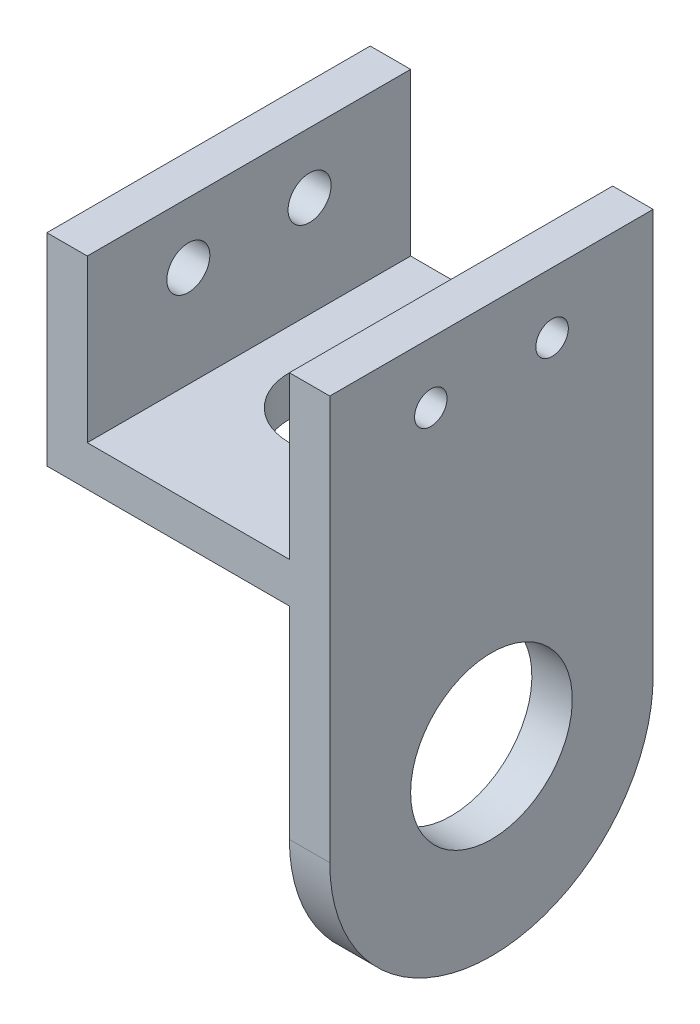
SolidWorks part; units mm, degrees
material "Nylon 101"
ref_plane "Front" through (0, 0, 0) normal (0, 0, 1) x (1, 0, 0)
ref_plane "Top" through (0, 0, 0) normal (0, 1, 0) x (1, 0, 0)
ref_plane "Right" through (0, 0, 0) normal (1, 0, 0) x (0, 0, -1)
sketch "Sketch1" plane through (0, 0, 0) normal (0, 0, 1) x (1, 0, 0)
  line L0 (0, 0) -> (6.35, 0)
  line L1 (6.35, 0) -> (6.35, 88.9)
  line L2 (6.35, 88.9) -> (0, 88.9)
  line L3 (0, 88.9) -> (0, 63.5)
  line L4 (0, 63.5) -> (-31.75, 63.5)
  line L5 (-31.75, 63.5) -> (-31.75, 88.9)
  line L6 (-31.75, 88.9) -> (-38.1, 88.9)
  line L7 (-38.1, 88.9) -> (-38.1, 57.15)
  line L8 (-38.1, 57.15) -> (0, 57.15)
  line L9 (0, 57.15) -> (0, 0)
  point P3 (0, 28.575)
  dimension "D1" = 6.35
  dimension "D2" = 28.575
  dimension "D3" = 31.75
  dimension "D4" = 6.35
  dimension "D5" = 6.35
  dimension "D6" = 25.4
  dimension "D8" = 6.35
extrude "Boss-Extrude1" add sketch "Sketch1" along normal blind 50.8
sketch "Sketch2" plane through (0, 0, 0) normal (-1, 0, 0) x (0, 0, 1)
  line L1 (50.8, 57.15) -> (50.8, 0) construction
  line L2 (50.8, 28.575) -> (0, 28.575) construction
  line L3 (0, 57.15) -> (0, 0) construction
  circle A0 centre (25.4, 28.575) radius 12.7
  dimension "D3" = 25.4
extrude "Cut-Extrude1" cut sketch "Sketch2" against normal blind 44.45
hole_wizard "1/4-20 Tapped Hole1" positions "Sketch3" profile "Sketch4" tap size "1/4-20" standard "ANSI Inch" end condition through all
sketch "Sketch3" plane through (0, 0, 0) normal (-1, 0, 0) x (0, 0, 1)
  line L2 (50.8, 88.9) -> (0, 88.9) construction
  line L3 (0, 88.9) -> (0, 63.5) construction
  point P0 (15.875, 79.375)
  point P2 (34.925, 79.375)
  dimension "D1" = 19.05
  dimension "D2" = 9.525
  dimension "D3" = 15.875
sketch "Sketch4" plane through (0, 79.375, 15.875) normal (0, 1, 0) x (0, 0, 1)
  line L0 (0, 0) -> (0, 6.35)
  line L1 (0, 6.35) -> (2.5527, 6.35)
  line L2 (2.5527, 6.35) -> (2.5527, 0)
  line L5 (2.5527, 0) -> (0, 0)
  line L11 (0, -6.35) -> (0, 107.95) construction
  dimension "Thru Tap Drill Dia." = 5.1054
  dimension "Thru Tap Drill Depth" = 6.35
cosmetic thread "Hole Thread1" parameters "D2"=6.35
cosmetic thread "Hole Thread2" parameters "D2"=6.35
sketch "Sketch5" plane through (-38.1, 0, 0) normal (-1, 0, 0) x (0, 0, 1)
  line L0 (50.8, 88.9) -> (0, 88.9) construction
  line L1 (50.8, 88.9) -> (50.8, 57.15) construction
  circle A0 centre (15.875, 79.375) radius 3.3782
  circle A1 centre (34.925, 79.375) radius 3.3782
  dimension "D4" = 6.7564
  dimension "D1" = 19.05
  dimension "D2" = 9.525
  dimension "D3" = 15.875
extrude "Cut-Extrude2" cut sketch "Sketch5" against normal blind 8.89
sketch "Sketch6" plane through (0, 63.5, 0) normal (0, 1, 0) x (1, 0, 0)
  line L0 (6.35, -50.8) -> (0, -50.8) construction
  line L2 (0, -50.8) -> (0, 0) construction
  circle A0 centre (-15.875, -25.4) radius 9.525
  dimension "D1" = 19.05
  dimension "D2" = 25.4
  dimension "D3" = 15.875
extrude "Cut-Extrude3" cut sketch "Sketch6" against normal blind 8.89
fillet "Fillet1" 2 edges at (3.175, 0, 50.8) (3.175, 0, 0) type full round first side face at (-12.7, 59.69, 50.8) second side face at (-12.7, 59.69, 0) middle face at (3.175, 0, 25.4)
